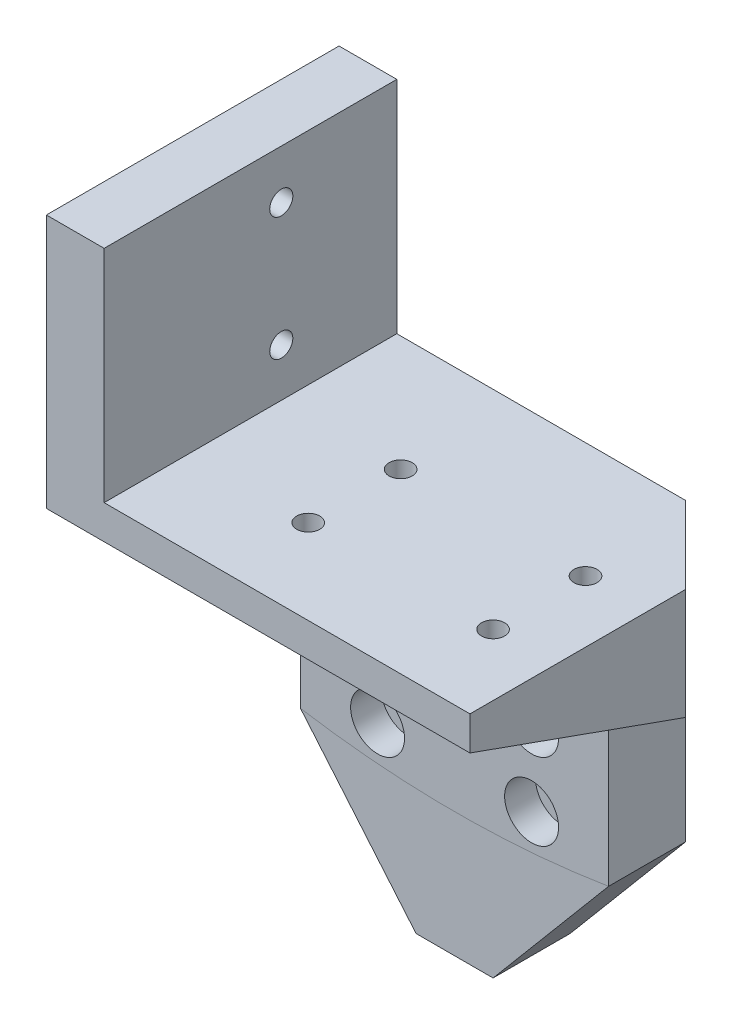
SolidWorks part; units mm, degrees
ref_plane "Plan de face" through (0, 0, 0) normal (0, 0, 1) x (1, 0, 0)
ref_plane "Plan de dessus" through (0, 0, 0) normal (0, 1, 0) x (1, 0, 0)
ref_plane "Plan de droite" through (0, 0, 0) normal (1, 0, 0) x (0, 0, -1)
sketch "Esquisse1" plane through (0, 0, 0) normal (0, 0, 1) x (1, 0, 0)
  line L0 (-20, -123.3896) -> (-20, -99.4)
  line L1 (-20, -99.4) -> (20, -99.4)
  line L2 (20, -99.4) -> (20, -123.3896)
  arc A0 (20, -123.3896) -> (-20, -123.3896) centre (0, 0) cw
  point P4 (0, -125)
  dimension "D1" = 125
  dimension "D3" = 25.6
  dimension "D2" = 40
extrude "Boss.-Extru.1" add sketch "Esquisse1" along normal blind 10
sketch "Esquisse2" plane through (0, 0, 10) normal (0, 0, 1) x (1, 0, 0)
  line L0 (0, -99.4) -> (0, -125) construction
  line L1 (20, -99.4) -> (-20, -99.4) construction
  line L2 (-10, -110) -> (-10, -120) construction
  line L3 (-10, -120) -> (10, -120) construction
  arc A0 (-20, -123.3896) -> (20, -123.3896) centre (0, 0) ccw construction
  circle A1 centre (-10, -110) radius 1.75
  circle A2 centre (-10, -120) radius 1.75
  circle A3 centre (10, -110) radius 1.75
  circle A4 centre (10, -120) radius 1.75
  point P16 (0, -112.2)
  point P17 (0, -120)
  dimension "D3" = 3.5
  dimension "D1" = 10
  dimension "D2" = 20
  dimension "D4" = 120
extrude "Enlèv. mat.-Extru.1" cut sketch "Esquisse2" against normal up to next
sketch "Esquisse4" plane through (0, 0, 10) normal (0, 0, 1) x (1, 0, 0)
  circle A0 centre (-10, -110) radius 3.5
  circle A1 centre (10, -110) radius 3.5
  circle A2 centre (10, -120) radius 3.5
  circle A3 centre (-10, -120) radius 3.5
  dimension "D1" = 7
extrude "Enlèv. mat.-Extru.2" cut sketch "Esquisse4" against normal blind 4
sketch "Esquisse5" plane through (0, -99.4, 0) normal (0, 1, 0) x (1, 0, 0)
  line L1 (-20, 0) -> (30, 0)
  line L2 (-20, 0) -> (-20, -38)
  line L3 (-20, -38) -> (30, -38)
  line L4 (30, 0) -> (30, -38)
  dimension "D1" = 50
  dimension "D2" = 38
extrude "Boss.-Extru.2" add sketch "Esquisse5" along normal blind 14.4
sketch "Esquisse6" plane through (0, -99.4, 0) normal (0, -1, 0) x (1, 0, 0)
  line L0 (20, 10) -> (-20, 10) construction
  line L1 (30, 38) -> (30, 0) construction
  circle A0 centre (-2, 27) radius 1.5
  circle A1 centre (22, 27) radius 1.5
  circle A2 centre (-2, 15) radius 1.5
  circle A3 centre (22, 15) radius 1.5
  dimension "D1" = 3
  dimension "D2" = 5
  dimension "D3" = 24
  dimension "D4" = 12
  dimension "D5" = 8
extrude "Enlèv. mat.-Extru.3" cut sketch "Esquisse6" against normal up to next
sketch "Esquisse7" plane through (0, -99.4, 0) normal (0, -1, 0) x (1, 0, 0)
  circle A0 centre (-2, 27) radius 3
  circle A1 centre (22, 27) radius 3
  circle A2 centre (22, 15) radius 3
  circle A3 centre (-2, 15) radius 3
  dimension "D1" = 6
extrude "Enlèv. mat.-Extru.4" cut sketch "Esquisse7" against normal offset from surface (9.4 mm away) 5 up to face at (22, -85, 28.5)
chamfer "Chanfrein1" distance 10 angle 45 1 edges at (30, -92.2, 0)
chamfer "Chanfrein2" distance 28 distance2 10 1 edges at (5, -99.4, 38) first distance on face at (-2, -99.4, 12)
sketch "Esquisse8" plane through (-20, 0, 0) normal (-1, 0, 0) x (0, 0, 1)
  line L0 (10, -99.4) -> (0, -99.4)
  line L1 (0, -85) -> (0, -123.3896) construction
  line L2 (0, -99.4) -> (0, -56.4)
  line L3 (0, -56.4) -> (38, -56.4)
  line L4 (38, -56.4) -> (38, -89.4)
  line L5 (38, -89.4) -> (10, -99.4)
  dimension "D1" = 43
extrude "Boss.-Extru.3" add sketch "Esquisse8" along normal blind 5
sketch "Esquisse9" plane through (-20, 0, 0) normal (1, 0, 0) x (0, 0, -1)
  line L4 (-38, -85) -> (0, -85)
  line L5 (0, -85) -> (0, -56.4)
  line L6 (0, -56.4) -> (-38, -56.4)
  line L7 (-38, -56.4) -> (-38, -85)
  line L8 (-38, -85) -> (0, -85)
  line L9 (0, -85) -> (0, -56.4)
  line L10 (0, -56.4) -> (-38, -56.4)
  line L11 (-38, -56.4) -> (-38, -85)
  dimension "D1" = 0
extrude "Boss.-Extru.4" add sketch "Esquisse9" along normal blind 2.5
chamfer "Chanfrein3" distance 5 angle 45 1 edges at (-20, -99.4, 5)
sketch "Esquisse10" plane through (-25, 0, 0) normal (-1, 0, 0) x (0, 0, 1)
  line L0 (38, -56.4) -> (0, -56.4) construction
  line L2 (13.5, -90) -> (16.5, -90) construction
  line L3 (13.5, -90) -> (16.5, -90) construction
  circle A0 centre (15, -62.75) radius 1.5
  circle A1 centre (15, -78.75) radius 1.5
  point P7 (15, -90)
  dimension "D1" = 3
  dimension "D2" = 16
  dimension "D3" = 6.35
extrude "Enlèv. mat.-Extru.5" cut sketch "Esquisse10" against normal up to next
sketch "Esquisse11" plane through (-25, 0, 0) normal (-1, 0, 0) x (0, 0, 1)
  circle A0 centre (15, -62.75) radius 3
  circle A1 centre (15, -78.75) radius 3
  dimension "D1" = 6
extrude "Enlèv. mat.-Extru.6" cut sketch "Esquisse11" against normal offset from surface (2.5 mm away) 5 up to face at (-17.5, -61.25, 15)
sketch "Esquisse12" plane through (0, 0, 10) normal (0, 0, 1) x (1, 0, 0)
  line L0 (0, 0) -> (0, -125) construction
  line L1 (0, -125) -> (0, -141.2) construction
  line L2 (-5, -141.2) -> (5, -141.2)
  line L3 (-5, -141.2) -> (-20, -123.3896)
  line L4 (20, -123.3896) -> (5, -141.2)
  arc A0 (-20, -123.3896) -> (20, -123.3896) centre (0, 0) ccw construction
  arc A1 (-20, -123.3896) -> (20, -123.3896) centre (0, 0) ccw
  point P9 (0, -141.2)
  dimension "D1" = 141.2
  dimension "D2" = 10
extrude "Boss.-Extru.5" add sketch "Esquisse12" against normal blind 10 separate body
sketch "Esquisse14" plane through (0, -141.2, 0) normal (0, -1, 0) x (1, 0, 0)
  line L0 (-5, 10) -> (5, 0) construction
  line L1 (-5, 0) -> (-5, 10) construction
  line L2 (-5, 10) -> (5, 10) construction
  circle A0 centre (0, 5) radius 2.75
  point P9 (-5, 10)
  point P10 (0, 5)
  dimension "D1" = 5.5
extrude "Enlèv. mat.-Extru.7" cut sketch "Esquisse14" against normal blind 2
